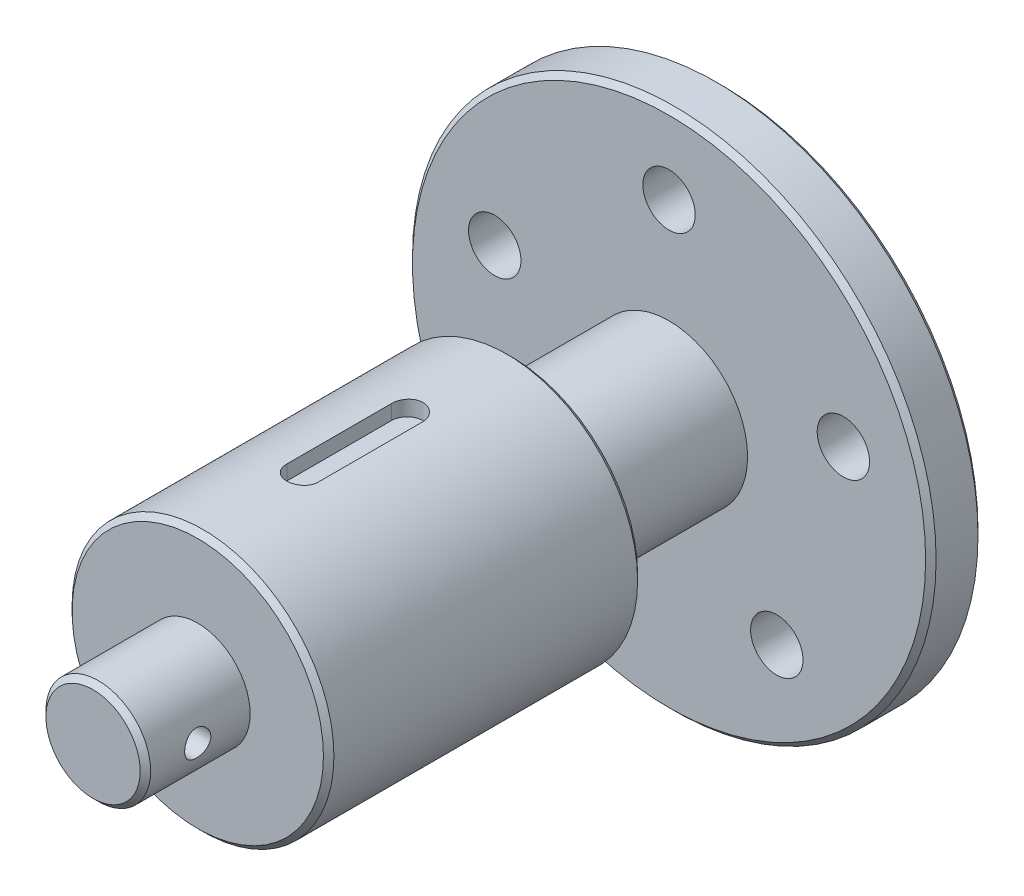
SolidWorks part; units mm, degrees
ref_plane "정면" through (0, 0, 0) normal (0, 0, 1) x (1, 0, 0)
ref_plane "윗면" through (0, 0, 0) normal (0, 1, 0) x (1, 0, 0)
ref_plane "우측면" through (0, 0, 0) normal (1, 0, 0) x (0, 0, -1)
sketch "스케치1" plane through (0, 0, 0) normal (0, 0, 1) x (1, 0, 0)
  circle A0 centre (0, 0) radius 50
  dimension "D1" = 100
extrude "보스-돌출1" add sketch "스케치1" along normal blind 10
sketch "스케치2" plane through (0, 0, 10) normal (0, 0, 1) x (1, 0, 0)
  circle A0 centre (0, 0) radius 15
  dimension "D1" = 30
extrude "보스-돌출2" add sketch "스케치2" along normal blind 28
sketch "스케치3" plane through (0, 0, 38) normal (0, 0, 1) x (1, 0, 0)
  circle A0 centre (0, 0) radius 16
  dimension "D1" = 32
extrude "보스-돌출3" add sketch "스케치3" along normal blind 2
sketch "스케치4" plane through (0, 0, 40) normal (0, 0, 1) x (1, 0, 0)
  circle A0 centre (0, 0) radius 25
  dimension "D1" = 50
extrude "보스-돌출4" add sketch "스케치4" along normal blind 60
sketch "스케치5" plane through (0, 0, 100) normal (0, 0, 1) x (1, 0, 0)
  circle A0 centre (0, 0) radius 10
  dimension "D1" = 20
extrude "보스-돌출5" add sketch "스케치5" along normal blind 20
chamfer "모따기1" distance 1 angle 45 5 edges at (10, 0, 120) (25, 0, 100) (25, 0, 40) (50, 0, 10) (50, 0, 0)
draft "구배27" type of draft neutral plane draft angle 45 faces to draft 1 face at (16, 0, 40) neutral plane through (0, 0, 40) neutral plane normal (0, 0, -1) parameters "D1"=45
sketch "스케치8" plane through (0, 0, 0) normal (0, 0, -1) x (-1, 0, 0)
  circle A0 centre (0, 0) radius 35
  dimension "D1" = 70
hole_wizard "Ø10.0 (10) 지름 구멍1" positions "스케치15" profile "스케치16" hole size "Ø10.0" standard "ISO" end condition up to next
sketch "스케치15" plane through (0, 0, 0) normal (0, 0, -1) x (-1, 0, 0)
  line L0 (0, 0) -> (0, 35) construction
  line L1 (0, 0) -> (-33.287, 10.8156) construction
  circle A0 centre (0, 0) radius 35 construction
  point P0 (0, 35)
  point P10 (-33.287, 10.8156)
  point P11 (-20.5725, -28.3156)
  point P12 (20.5725, -28.3156)
  point P13 (33.287, 10.8156)
  dimension "D1" = 72
sketch "스케치16" plane through (0, 35, 0) normal (1, 0, 0) x (0, 1, 0)
  line L0 (0, 0) -> (0, 10)
  line L1 (0, 10) -> (5, 10)
  line L2 (5, 10) -> (5, 0)
  line L5 (5, 0) -> (0, 0)
  line L11 (0, -6.35) -> (0, 107.95) construction
  dimension "관통 구멍 지름" = 10
  dimension "관통 구멍 깊이" = 10
ref_plane "평면1" through (0, 0, 100) normal (0, 0, 1) x (1, 0, 0)
ref_plane "평면2" through (0, 25, 0) normal (0, 1, 0) x (1, 0, 0)
sketch "스케치17" plane through (0, 25, 0) normal (0, 1, 0) x (1, 0, 0)
  line L0 (-3, -60) -> (-3, -80)
  line L1 (3, -60) -> (3, -80)
  line L2 (-9, -120) -> (9, -120) construction
  arc A0 (3, -60) -> (-3, -60) centre (0, -60) ccw
  arc A1 (-3, -80) -> (3, -80) centre (0, -80) ccw
  dimension "D1" = 6
  dimension "D2" = 6
  dimension "D3" = 20
  dimension "D4" = 40
extrude "컷-돌출1" cut sketch "스케치17" against normal blind 3
ref_plane "평면3" through (-10, 0, 0) normal (1, 0, 0) x (0, 0, -1)
hole_wizard "Ø5.0 (5) 지름 구멍1" positions "스케치19" profile "스케치20" hole size "Ø5.0" standard "ISO" end condition through all
sketch "스케치19" plane through (-10, 0, 0) normal (1, 0, 0) x (0, 0, -1)
  line L0 (-100, 26.4) -> (-100, -26.4) construction
  line L1 (-100, 10) -> (-119, 10) construction
  point P0 (-110, 0)
  dimension "D1" = 10
  dimension "D2" = 10
sketch "스케치20" plane through (-10, 0, 110) normal (0, 1, 0) x (0, 0, 1)
  line L0 (0, 0) -> (0, 60)
  line L1 (0, 60) -> (2.5, 60)
  line L2 (2.5, 60) -> (2.5, 0)
  line L5 (2.5, 0) -> (0, 0)
  line L11 (0, -6.35) -> (0, 107.95) construction
  dimension "관통 구멍 지름" = 5
  dimension "관통 구멍 깊이" = 60
